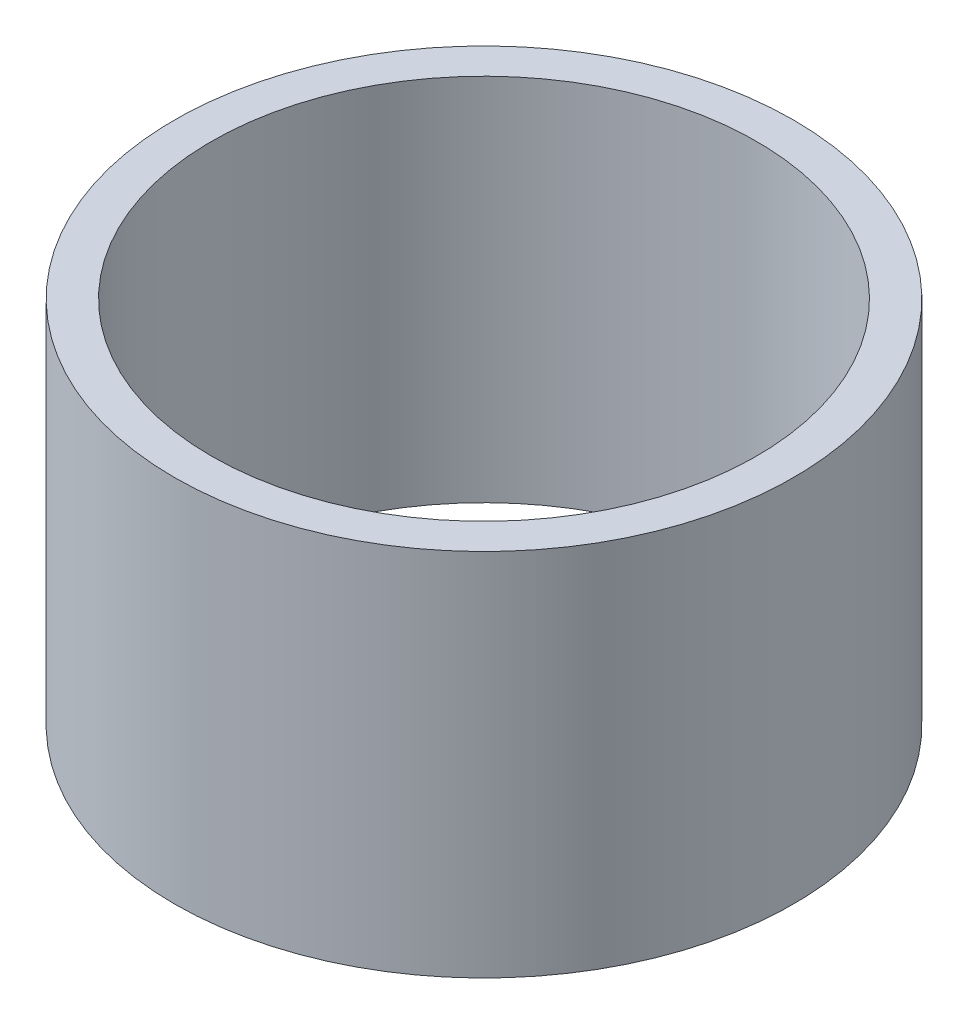
SolidWorks part; units mm, degrees
ref_plane "Front Plane" through (0, 0, 0) normal (0, 0, 1) x (1, 0, 0)
ref_plane "Top Plane" through (0, 0, 0) normal (0, 1, 0) x (1, 0, 0)
ref_plane "Right Plane" through (0, 0, 0) normal (1, 0, 0) x (0, 0, -1)
sketch "Sketch1" plane through (0, 0, 0) normal (0, 1, 0) x (1, 0, 0)
  circle A0 centre (0, 0) radius 55
  dimension "SLEEVE_OD" = 110
extrude "Boss-Extrude1" add sketch "Sketch1" along normal blind 65.6178
sketch "Sketch2" plane through (0, 0, 0) normal (0, 1, 0) x (1, 0, 0)
  circle A0 centre (0, 0) radius 48.4254
  dimension "BORE_D" = 96.8508
extrude "Cut-Extrude1" cut sketch "Sketch2" along normal through all
chamfer "Chamfer1" distance 2.9407 angle 60 rebuild error yes
